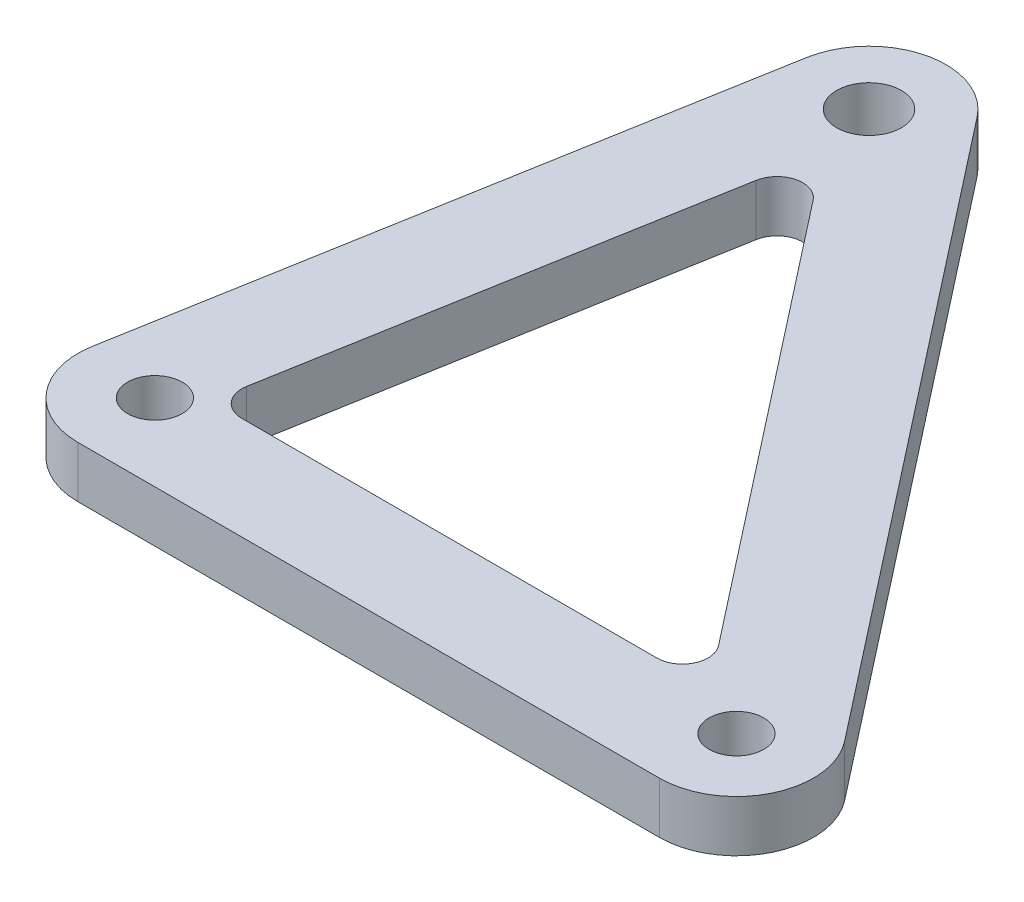
SolidWorks part; units mm, degrees
ref_plane "Front Plane" through (0, 0, 0) normal (0, 0, 1) x (1, 0, 0)
ref_plane "Top Plane" through (0, 0, 0) normal (0, 1, 0) x (1, 0, 0)
ref_plane "Right Plane" through (0, 0, 0) normal (1, 0, 0) x (0, 0, -1)
sketch "Sketch1" plane through (0, 0, 0) normal (0, 1, 0) x (1, 0, 0)
  line L0 (0, 0) -> (71.882, 0) construction
  line L1 (71.882, 0) -> (13.2224, 75.044) construction
  line L2 (13.2224, 75.044) -> (0, 0) construction
  line L3 (6.3163, 90.7407) -> (-10.6935, -5.7991)
  line L4 (-7.5666, -9.525) -> (84.9054, -9.525)
  line L5 (87.4068, -4.3947) -> (11.9446, 92.1451)
  line L6 (19.503, 61.8536) -> (61.3601, 8.3053)
  line L7 (58.8586, 3.175) -> (7.5666, 3.175)
  line L8 (4.4398, 6.9009) -> (13.8747, 60.4492)
  circle A0 centre (0, 0) radius 3.3782
  circle A1 centre (13.2224, 75.044) radius 4
  circle A2 centre (71.882, 0) radius 3.3782
  arc A3 (61.3601, 8.3053) -> (58.8586, 3.175) centre (58.8586, 6.35) cw
  arc A4 (7.5666, 3.175) -> (4.4398, 6.9009) centre (7.5666, 6.35) cw
  arc A5 (19.503, 61.8536) -> (13.8747, 60.4492) centre (17.0016, 59.8983) ccw
  arc A6 (87.4068, -4.3947) -> (84.9054, -9.525) centre (84.9054, -6.35) cw
  arc A7 (-7.5666, -9.525) -> (-10.6935, -5.7991) centre (-7.5666, -6.35) cw
  arc A8 (11.9446, 92.1451) -> (6.3163, 90.7407) centre (9.4431, 90.1898) ccw
  circle A9 centre (71.882, 0) radius 9.525
  circle A10 centre (0, 0) radius 9.525
  circle A11 centre (13.2224, 75.044) radius 9.525
  point P18 (9.1573, 33.6751)
  dimension "D4" = 6.7564
  dimension "D5" = 8
  dimension "D6" = 9.525
  dimension "D12" = 3.175
  dimension "D1" = 71.882
  dimension "D2" = 76.2
  dimension "D3" = 95.25
  dimension "D7" = 9.525
  dimension "D8" = 9.525
  dimension "D9" = 12.7
  dimension "D10" = 12.7
  dimension "D11" = 12.7
extrude "Boss-Extrude2" add sketch "Sketch1" along normal blind 6.35 contours A11 L3 A10 L8 A5 L6 A3 L7 L4 A9 L5 | A10 L7 A4 L8 A0 | A9 A2 | A11 A1 region at (12.2824, 0, -64.2929) region at (10.9816, 0, -84.0243) region at (-3.9513, 0, -8.3698) region at (80.633, 0, -3.0144)
